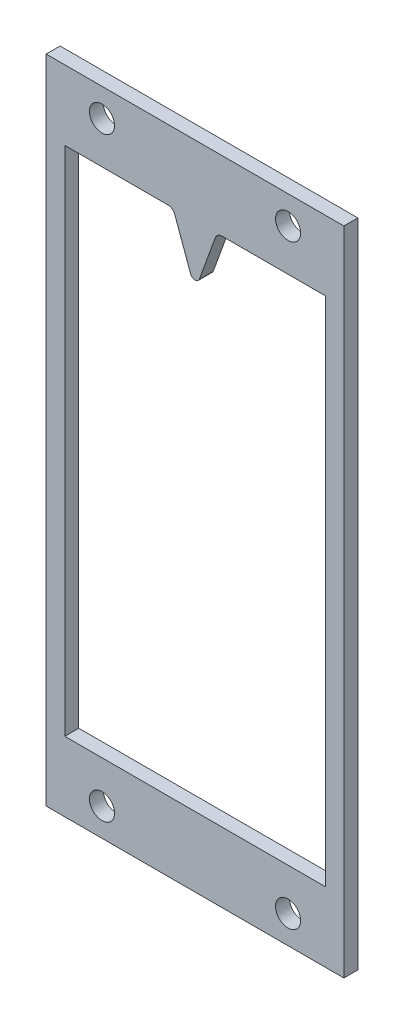
SolidWorks part; units mm, degrees
material "ABS"
ref_plane "Front Plane" through (0, 0, 0) normal (0, 0, 1) x (1, 0, 0)
ref_plane "Top Plane" through (0, 0, 0) normal (0, 1, 0) x (1, 0, 0)
ref_plane "Right Plane" through (0, 0, 0) normal (1, 0, 0) x (0, 0, -1)
sketch "Sketch1" plane through (0, 0, 0) normal (0, 0, 1) x (1, 0, 0)
  line L0 (28, 15) -> (28, 0) construction
  line L1 (0, 0) -> (23.2684, 0)
  line L2 (0, 0) -> (0, -110)
  line L3 (0, -110) -> (56, -110)
  line L4 (56, 0) -> (56, -110)
  line L5 (-4, 15) -> (60, 15)
  line L6 (-4, 15) -> (-4, -125)
  line L7 (-4, -125) -> (60, -125)
  line L8 (60, 15) -> (60, -125)
  line L9 (-4, -55) -> (60, -55) construction
  line L10 (28.9397, -10.4182) -> (32.7316, 0)
  line L11 (27.0603, -10.4182) -> (23.2684, 0)
  line L12 (32.7316, 0) -> (56, 0)
  line L13 (28, -13) -> (28, -125) construction
  circle A0 centre (8, 9) radius 2.6993
  circle A1 centre (48, 9) radius 2.6993
  circle A2 centre (48, -119) radius 2.6993
  circle A3 centre (8, -119) radius 2.6993
  arc A4 (28.9397, -10.4182) -> (27.0603, -10.4182) centre (28, -10.0762) cw
  point P9 (28, -125)
  point P10 (28, -110)
  point P11 (-4, -55)
  point P12 (0, -55)
  dimension "D9" = 1
  dimension "D1" = 56
  dimension "D2" = 110
  dimension "D3" = 64
  dimension "D4" = 140
  dimension "D5" = 12
  dimension "D6" = 6
  dimension "D8" = 13
  dimension "D7" = 20
extrude "Boss-Extrude1" add sketch "Sketch1" along normal blind 3
fillet "Fillet1" radius 1.5 2 edges at (23.2684, 0, 1.5) (32.7316, 0, 1.5)
equation "\"Depth\"= 90mm"
equation "\"Height\"= 140mm"
equation "\"Width\"= 64mm"
equation "\"D3@Sketch1\"=\"Width\""
equation "\"D4@Sketch1\"=\"Height\""
